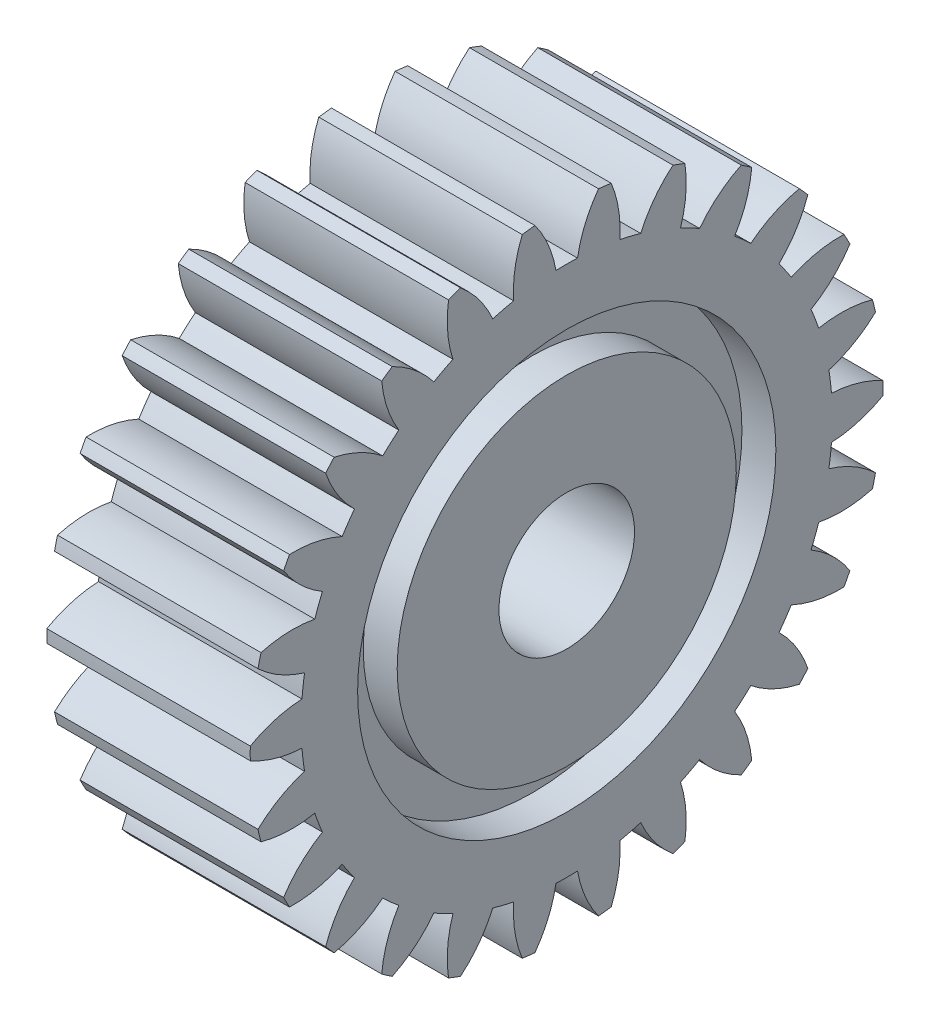
SolidWorks part; units mm, degrees
ref_plane "Plane1" through (0, 0, 0) normal (0, 0, 1) x (1, 0, 0)
ref_plane "Plane2" through (0, 0, 0) normal (0, 1, 0) x (1, 0, 0)
ref_plane "Plane3" through (0, 0, 0) normal (1, 0, 0) x (0, 0, -1)
other "Configuration Table"
sketch "HoldingSke" plane through (0, 0, 0) normal (0, 1, 0) x (1, 0, 0)
  line L0 (0, 0) -> (0.8988, -0.4384)
  line L1 (-15, 0) -> (100, 0) construction
  line L2 (0, 0) -> (-2.1039, 2.3779)
  line L3 (0, 0) -> (-11.863, 4.5341)
  line L4 (0, 0) -> (7.762, 3.7858)
  line L5 (0, 0) -> (-16.8652, -6.2902)
  line L6 (0, 0) -> (-7.4607, -5.0337)
  line L7 (-2.1039, 2.3779) -> (1.7706, 19.956)
  line L8 (-76.2, 54.61) -> (-75.2, 54.61)
  line L9 (-71.009, 38.7566) -> (-53.1078, 45.2721)
  line L10 (-76.2, 71.12) -> (104.1128, 71.12)
  line L11 (0, 0) -> (-9, 0)
  line L12 (-76.2, 101.6) -> (-76.162, 101.6)
  line L13 (24.9733, 27.94) -> (52.9518, 28.4284)
  line L14 (24.9733, 27.94) -> (24.9743, 27.94)
  line L15 (24.9733, 27.94) -> (100.4006, 29.5858)
  line L16 (-63.627, -1) -> (-12.827, -1)
  circle A0 centre (0, 0) radius 3
  circle A1 centre (0, 0) radius 7.5
  circle A2 centre (0, 0) radius 7.5
  circle A3 centre (0, 0) radius 3
  dimension "Num_teeth" = 26
  dimension "Pitch_radius" = 180.3128
  dimension "Width" = 9
  dimension "Thickness" = 9
sketch "BasProSke" plane through (0, 0, 0) normal (0, 1, 0) x (1, 0, 0)
  line L0 (-10, 0) -> (60, 0) construction
  line L1 (0, 0) -> (0, 14)
  line L2 (0, 0) -> (9, 0)
  line L3 (9, 0) -> (9, 14)
  line L4 (9, 14) -> (0, 14)
  dimension "Thickness" = 9
  dimension "Diameter" = 28
revolve "Base-Revolve" add sketch "BasProSke" angle 360 about L0
sketch "TooCutSke" plane through (0, 0, 0) normal (1, 0, 0) x (0, 0, -1)
  line L1 (0, 0) -> (0, 107) construction
  line L2 (0, 0) -> (-0.8514, 12.9721) construction
  line L3 (0, 0) -> (-3.1292, 25.771) construction
  line L4 (-0.8514, 12.9721) -> (-1.5646, 12.8855) construction
  arc A0 (0.477, 11.7393) -> (-0.477, 11.7393) centre (0, 0) ccw
  arc A1 (1.4241, 13.9529) -> (-1.4241, 13.9529) centre (0, 0) ccw
  circle A2 centre (0, 0) radius 13 construction
  circle A3 centre (0, 0) radius 12.216 construction
  arc A4 (-0.477, 11.7393) -> (-1.4241, 13.9529) centre (-5.6014, 10.8561) ccw
  arc A5 (1.4241, 13.9529) -> (0.477, 11.7393) centre (5.6014, 10.8561) ccw
extrude "ToothCut" cut sketch "TooCutSke" along normal through all
fillet "Breaks" [suppressed] radius 0.02 tangent propagation no
fillet "RootFillets" [suppressed] radius 0.251
pattern_circular "TeethCuts" count 26 every 13.846 about axis through (-10, 0, 0) along (1, 0, 0) of "ToothCut", "RootFillets", "Breaks"
sketch "HubNeaOneSke" plane through (0, 0, 0) normal (-1, 0, 0) x (0, 0, 1)
  circle A0 centre (0, 0) radius 7.5
  dimension "Diameter" = 15
extrude "HubNearOne" add sketch "HubNeaOneSke" along normal blind 9.0001
sketch "HubNeaBotSke" plane through (0, 0, 0) normal (-1, 0, 0) x (0, 0, 1)
  circle A0 centre (0, 0) radius 7.5
  dimension "Diameter" = 15
extrude "HubNearBoth" [suppressed] add sketch "HubNeaBotSke" along normal blind 4.5
ref_plane "FarPln" through (9, 0, 0) normal (1, 0, 0) x (0, 0, -1)
sketch "HubFarSke" plane through (9, 0, 0) normal (1, 0, 0) x (0, 0, -1)
  circle A0 centre (0, 0) radius 7.5
  dimension "Diameter" = 15
extrude "HubFar" [suppressed] add sketch "HubFarSke" along normal blind 4.5
sketch "BorSke" plane through (0, 0, 0) normal (1, 0, 0) x (0, 0, -1)
  circle A0 centre (0, 0) radius 3
  dimension "Diameter" = 6
extrude "Bore" cut sketch "BorSke" along normal mid plane 36.0001
sketch "KeySke" plane through (0, 0, 0) normal (1, 0, 0) x (0, 0, -1)
  line L0 (-1, 0) -> (-1, 4)
  line L1 (-1, 4) -> (1, 4)
  line L2 (1, 4) -> (1, 0)
  line L3 (0, 0) -> (0, 34) construction
  line L4 (-1, 0) -> (1, 0)
  dimension "Width" = 2
extrude "Keyway" [suppressed] cut sketch "KeySke" along normal mid plane 36.0001
pattern_circular "Keyway2" [suppressed] count 2 every 90 about axis through (-10, 0, 0) along (1, 0, 0) reverse direction yes
sketch "Sketch1" plane through (0, 0, 0) normal (0, 0, 1) x (1, 0, 0)
  line L1 (-9.0001, 7.5) -> (0, 7.5)
  line L2 (-9.0001, 7.5) -> (-9.0001, -7.5238)
  line L3 (-9.0001, -7.5238) -> (0, -7.5238)
  line L4 (0, 7.5) -> (0, -7.5238)
  line L5 (0, 7.5) -> (0, -7.5) construction
  dimension "D1" = 0
extrude "Cut-Extrude1" cut sketch "Sketch1" against normal through all both and the other way through all
sketch "Sketch2" plane through (9, 0, 0) normal (1, 0, 0) x (0, 0, -1)
  circle A0 centre (0, 0) radius 9.25
  circle A2 centre (0, 0) radius 7.5
  dimension "D1" = 18.5
  dimension "D2" = 15
extrude "Cut-Extrude2" cut sketch "Sketch2" against normal blind 1.5
extrude "Cut-Extrude3" cut sketch "Sketch2<2>" along normal blind 1.5 from surface starting at face at (0, 0, 0)
sketch "Sketch2<2>" plane through (9, 0, 0) normal (1, 0, 0) x (0, 0, -1) same geometry as "Sketch2"
equation "' \"Module@HoldingSke\" = 6.35"
equation "' \"Num_teeth@HoldingSke\" = 12"
equation "' \"Ap@HoldingSke\" =  20"
equation "' \"Ap@HoldingSke\" = 20"
equation "' \"Width@HoldingSke\" = 0.5 * 25.4"
equation "' \"Hub_dia@HoldingSke\"= 1 * 25.4"
equation "' \"Hub_dia@HoldingSke\" = 1 * 25.4"
equation "' \"Overall_len@HoldingSke\" = 1.0 * 25.4"
equation "' \"Bore@HoldingSke\" = 0.75 * 25.4"
equation "' \"T_dim@HoldingSke\" = 0.1 * 25.4"
equation "' \"Width@KeySke\" = 0.25 * 25.4"
equation "' \"Show_teeth@HoldingSke\" = 13"
equation "' \"Backlash@HoldingSke\" = 0.009 * 25.4"
equation "' \"Addendum_fac@HoldingSke\" = 1.0"
equation "' \"Dedendum_fac@HoldingSke\" = 1.25"
equation "' \"Dedendum_add@HoldingSke\" = 0.00005 * 25.4"
equation "' \"Clearance_fac@HoldingSke\" = 0.25"
equation "\"Pitch@HoldingSke\" = 1 / \"Module@HoldingSke\""
equation "\"Overcut_dia@TooCutSke\" = (\"Num_teeth@HoldingSke\" + 2 * \"Addendum_fac@HoldingSke\") / \"Pitch@HoldingSke\" + 0.002 * 25.4"
equation "\"Pitch_dia@TooCutSke\" = \"Num_teeth@HoldingSke\" / \"Pitch@HoldingSke\""
equation "\"Base_dia@TooCutSke\" = \"Num_teeth@HoldingSke\" / \"Pitch@HoldingSke\" * cos((\"Ap@HoldingSke\"  * 3.14159265 / 180))"
equation "\"Root_dia@TooCutSke\" = (\"Num_teeth@HoldingSke\" + 2) / \"Pitch@HoldingSke\" - 2 * (\"Addendum_fac@HoldingSke\" + \"Dedendum_fac@HoldingSke\") / \"Pitch@HoldingSke\" - \"Dedendum_add@HoldingSke\" * 2"
equation "\"Half_ang@TooCutSke\" = 180 / \"Num_teeth@HoldingSke\""
equation "\"Half_CT@TooCutSke\" = \"Num_teeth@HoldingSke\" / \"Pitch@HoldingSke\" * sin((3.14159265 / 2 / \"Num_teeth@HoldingSke\")) / 2 - 7 * \"Backlash@HoldingSke\" / 4"
equation "\"Flank_rad@TooCutSke\" = \"Num_teeth@HoldingSke\" / \"Pitch@HoldingSke\" / 5"
equation "\"Radius@RootFillets\" = \"Clearance_fac@HoldingSke\" / \"Pitch@HoldingSke\" + \"Dedendum_add@HoldingSke\""
equation "\"Break_rad@Breaks\" = 0.02 / \"Pitch@HoldingSke\""
equation "\"Thickness@HoldingSke\" = \"Width@HoldingSke\""
equation "\"OAL@HoldingSke\" = \"Thickness@HoldingSke\""
equation "\"MHD@HoldingSke\" = (\"Num_teeth@HoldingSke\" + 2) / \"Pitch@HoldingSke\" - 2 * (\"Addendum_fac@HoldingSke\" + \"Dedendum_fac@HoldingSke\")  / \"Pitch@HoldingSke\" - \"Dedendum_add@HoldingSke\" * 2"
equation "\"MBD@HoldingSke\" = (\"Num_teeth@HoldingSke\" + 2) / \"Pitch@HoldingSke\" - 2 * (\"Addendum_fac@HoldingSke\" + \"Dedendum_fac@HoldingSke\")  / \"Pitch@HoldingSke\" - \"Dedendum_add@HoldingSke\" * 2 - 0.002 * 25.4"
equation "\"MHD@HoldingSke\" = ((sgn( \"MHD@HoldingSke\" - \"Hub_dia@HoldingSke\" )-1)*( \"MHD@HoldingSke\" - \"Hub_dia@HoldingSke\" ))/-2+ \"Hub_dia@HoldingSke\""
equation "\"MBD@HoldingSke\" = ((sgn( \"MBD@HoldingSke\" - \"Bore@HoldingSke\" )-1)*( \"MBD@HoldingSke\" - \"Bore@HoldingSke\" ))/-2+ \"Bore@HoldingSke\""
equation "\"OAL@HoldingSke\" = ((sgn( \"OAL@HoldingSke\" - \"Overall_len@HoldingSke\" )+1)*( \"OAL@HoldingSke\" - \"Overall_len@HoldingSke\" ))/2 + \"Overall_len@HoldingSke\" + 0.000002 * 25.4"
equation "\"Num_teeth@TeethCuts\" = int( \"Show_teeth@HoldingSke\" ) + 1"
equation "\"Num_teeth@TeethCuts\" = ((sgn( \"Num_teeth@TeethCuts\" - \"Num_teeth@HoldingSke\" )-1)*( \"Num_teeth@TeethCuts\" - \"Num_teeth@HoldingSke\" ))/-2+ \"Num_teeth@HoldingSke\""
equation "\"Num_teeth@TeethCuts\" = ((sgn( \"Num_teeth@TeethCuts\" - 2.0)+1)*( \"Num_teeth@TeethCuts\" - 2.0))/2 +2.0"
equation "\"Angle@TeethCuts\" = 360.0 / \"Num_teeth@HoldingSke\""
equation "\"Diameter@BasProSke\" = (\"Num_teeth@HoldingSke\" + 2 * \"Addendum_fac@HoldingSke\") / \"Pitch@HoldingSke\""
equation "\"Thickness@BasProSke\"  = \"Thickness@HoldingSke\""
equation "' \"Fillet_rad@BasProSke\" =  \"Thickness@HoldingSke\" * 0.05"
equation "' \"Fillet_rad@BasProSke\" = \"Thickness@HoldingSke\" * 0.05"
equation "\"MHD@HoldingSke\" = ((sgn( \"MHD@HoldingSke\" - \"Root_dia@TooCutSke\" )-1)*( \"MHD@HoldingSke\" - \"Root_dia@TooCutSke\" ))/-2+ \"Root_dia@TooCutSke\""
equation "\"Diameter@HubNeaOneSke\" = \"MHD@HoldingSke\""
equation "\"Length@HubNearOne\" = \"OAL@HoldingSke\" - \"Thickness@BasProSke\""
equation "\"Diameter@HubNeaBotSke\" = \"MHD@HoldingSke\""
equation "\"Length@HubNearBoth\" = ( \"OAL@HoldingSke\" - \"Thickness@BasProSke\" ) / 2.0"
equation "\"Thickness@FarPln\" = \"Thickness@BasProSke\""
equation "\"Diameter@HubFarSke\" = \"MHD@HoldingSke\""
equation "\"Length@HubFar\" = ( \"OAL@HoldingSke\" - \"Thickness@BasProSke\" ) / 2.0"
equation "\"Diameter@BorSke\" = \"MBD@HoldingSke\""
equation "\"D1@Bore\" = \"OAL@HoldingSke\" * 2.0"
equation "\"D1@Keyway\" = \"OAL@HoldingSke\" * 2.0"
equation "\"Offset@KeySke\" = \"T_dim@HoldingSke\" + \"MBD@HoldingSke\" / 2.0"
